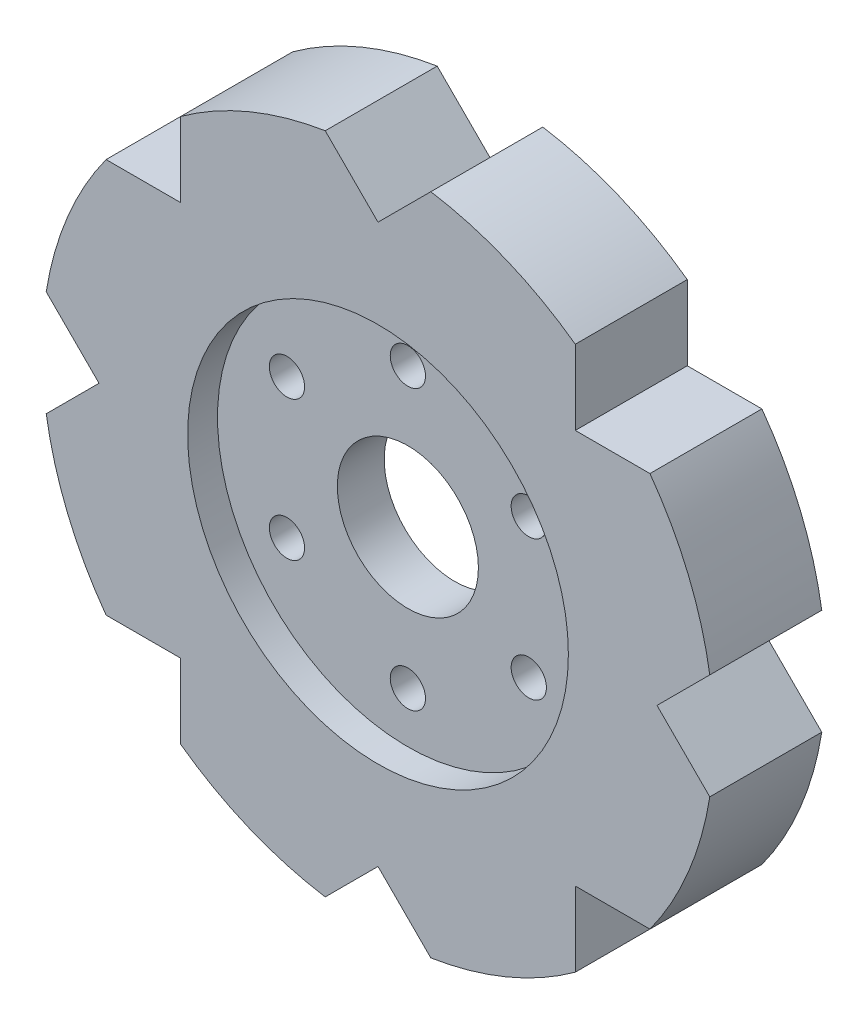
SolidWorks part; units mm, degrees
material "PE High Density Film"
ref_plane "Front Plane" through (0, 0, 0) normal (0, 0, 1) x (1, 0, 0)
ref_plane "Top Plane" through (0, 0, 0) normal (0, 1, 0) x (1, 0, 0)
ref_plane "Right Plane" through (0, 0, 0) normal (1, 0, 0) x (0, 0, -1)
sketch "Sketch1" plane through (0, 0, 0) normal (0, 0, 1) x (1, 0, 0)
  line L0 (0, 0) -> (0, 57.15) construction
  line L1 (-8.9803, 56.44) -> (0, 47.4598)
  line L2 (0, 47.4598) -> (8.9803, 56.44)
  line L3 (33.5591, 46.2591) -> (33.5591, 33.5591)
  line L4 (33.5591, 33.5591) -> (46.2591, 33.5591)
  line L5 (56.44, 8.9803) -> (47.4598, 0)
  line L6 (47.4598, 0) -> (56.44, -8.9803)
  line L7 (46.2591, -33.5591) -> (33.5591, -33.5591)
  line L8 (33.5591, -33.5591) -> (33.5591, -46.2591)
  line L9 (8.9803, -56.44) -> (0, -47.4598)
  line L10 (0, -47.4598) -> (-8.9803, -56.44)
  line L11 (-33.5591, -46.2591) -> (-33.5591, -33.5591)
  line L12 (-33.5591, -33.5591) -> (-46.2591, -33.5591)
  line L13 (-56.44, -8.9803) -> (-47.4598, 0)
  line L14 (-47.4598, 0) -> (-56.44, 8.9803)
  line L15 (-46.2591, 33.5591) -> (-33.5591, 33.5591)
  line L16 (-33.5591, 33.5591) -> (-33.5591, 46.2591)
  arc A0 (-56.44, -8.9803) -> (-46.2591, -33.5591) centre (0, 0) ccw
  arc A1 (-46.2591, 33.5591) -> (-56.44, 8.9803) centre (0, 0) ccw
  arc A2 (-33.5591, -46.2591) -> (-8.9803, -56.44) centre (0, 0) ccw
  arc A3 (8.9803, -56.44) -> (33.5591, -46.2591) centre (0, 0) ccw
  arc A4 (46.2591, -33.5591) -> (56.44, -8.9803) centre (0, 0) ccw
  arc A5 (56.44, 8.9803) -> (46.2591, 33.5591) centre (0, 0) ccw
  arc A6 (33.5591, 46.2591) -> (8.9803, 56.44) centre (0, 0) ccw
  arc A7 (-8.9803, 56.44) -> (-33.5591, 46.2591) centre (0, 0) ccw
  point P30 (0, 0)
  dimension "D1" = 114.3
  dimension "D2" = 45
  dimension "D3" = 12.7
  dimension "D4" = 8
extrude "Boss-Extrude1" add sketch "Sketch1" along normal blind 19.05
sketch "Sketch2" plane through (0, 0, 19.05) normal (0, 0, 1) x (1, 0, 0)
  circle A0 centre (0, 0) radius 12
  dimension "D1" = 24
extrude "Cut-Extrude1" cut sketch "Sketch2" against normal through all contours A0 region at (0, 0, 19.05)
sketch "Sketch3" plane through (0, 0, 19.05) normal (0, 0, 1) x (1, 0, 0)
  circle A0 centre (0, 0) radius 32.385
  dimension "D1" = 64.77
extrude "Cut-Extrude2" cut sketch "Sketch3" against normal blind 5.08
sketch "Sketch4" plane through (0, 0, 0) normal (0, 0, -1) x (-1, 0, 0)
  circle A0 centre (0, 0) radius 28.4
  dimension "D1" = 56.8
extrude "Cut-Extrude3" cut sketch "Sketch4" against normal blind 6
sketch "Sketch5" plane through (0, 0, 6) normal (0, 0, -1) x (-1, 0, 0)
  line L0 (0, 0) -> (0, 23.75) construction
  circle A0 centre (0, 0) radius 23.75 construction
  circle A1 centre (0, 23.75) radius 2.6
  circle A2 centre (20.5681, 11.875) radius 2.6
  circle A3 centre (20.5681, -11.875) radius 2.6
  circle A4 centre (0, -23.75) radius 2.6
  circle A5 centre (-20.5681, -11.875) radius 2.6
  circle A6 centre (-20.5681, 11.875) radius 2.6
  point P17 (0, 0)
  dimension "D1" = 47.5
  dimension "D2" = 5.2
  dimension "D3" = 6
hole_wizard "Ø6.0mm Dowel Hole1" positions "Sketch6" profile "Sketch8" hole size "Ø6.0" standard "ANSI Metric" end condition through all
sketch "Sketch6" plane through (0, 0, 6) normal (0, 0, -1) x (-1, 0, 0)
  point P0 (0, 23.75)
  point P3 (20.5681, 11.875)
  point P6 (20.5681, -11.875)
  point P9 (0, -23.75)
  point P13 (-20.5681, 11.875)
  point P16 (-20.5681, -11.875)
sketch "Sketch8" plane through (0, 23.75, 6) normal (1, 0, 0) x (0, 1, 0)
  line L0 (0, 0) -> (0, 13.05)
  line L1 (0, 13.05) -> (3, 13.05)
  line L2 (3, 13.05) -> (3, 0)
  line L5 (3, 0) -> (0, 0)
  line L11 (0, -6.35) -> (0, 107.95) construction
  dimension "Thru Hole Dia." = 6
  dimension "Thru Hole Depth" = 13.05
